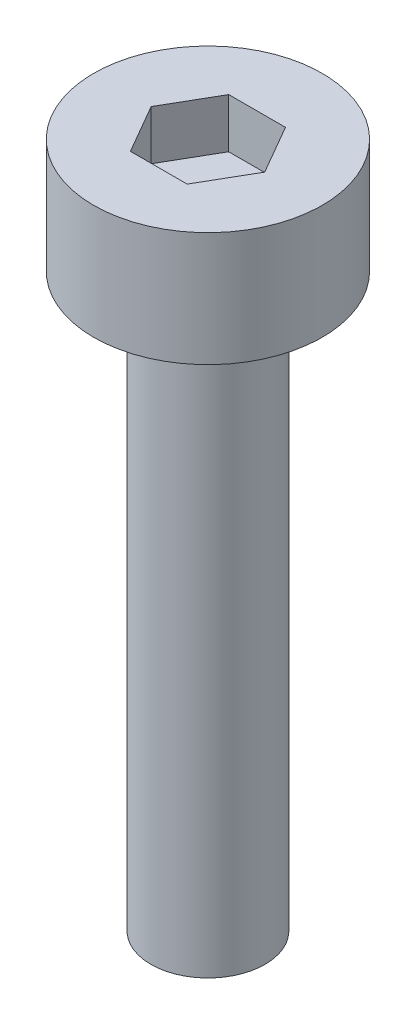
SolidWorks part; units mm, degrees
ref_plane "Front Plane" through (0, 0, 0) normal (0, 0, 1) x (1, 0, 0)
ref_plane "Top Plane" through (0, 0, 0) normal (0, 1, 0) x (1, 0, 0)
ref_plane "Right Plane" through (0, 0, 0) normal (1, 0, 0) x (0, 0, -1)
sketch "Sketch1" plane through (0, 0, 0) normal (0, 1, 0) x (1, 0, 0)
  circle A0 centre (0, 0) radius 1.5
  dimension "D1" = 3
extrude "ScrewShaft" add sketch "Sketch1" along normal blind 15
sketch "Sketch2" plane through (0, 15, 0) normal (0, 1, 0) x (1, 0, 0)
  circle A0 centre (0, 0) radius 3
  dimension "D1" = 6
extrude "Boss-Extrude2" add sketch "Sketch2" along normal blind 3
sketch "Sketch3" plane through (0, 18, 0) normal (0, 1, 0) x (1, 0, 0)
  line L0 (0, 0) -> (0, 1.29) construction
  line L1 (1.4896, 0) -> (0.7448, 1.29)
  line L2 (0.7448, 1.29) -> (-0.7448, 1.29)
  line L3 (-0.7448, 1.29) -> (-1.4896, 0)
  line L4 (-1.4896, 0) -> (-0.7448, -1.29)
  line L5 (-0.7448, -1.29) -> (0.7448, -1.29)
  line L6 (0.7448, -1.29) -> (1.4896, 0)
  circle A0 centre (0, 0) radius 1.29 construction
  dimension "D1" = 2.58
extrude "Cut-Extrude1" cut sketch "Sketch3" against normal blind 1.3
equation "\"X-ROD-SPACING\"=45"
equation "\"Y-ROD-SPACING\"=75"
equation "\"Z-ROD-SPACING\"=17.5"
equation "\"Y-BED-OFFSET\"=2"
equation "\"Y-BED-ROD-INSET\"=3.5"
equation "\"T-SLOT-NUT-FILLET-RADIUS\"=0.25"
equation "\"T-SLOT-SCREW-SHAFT-RADIUS\"=1.75"
equation "\"T-SLOT-SCREW-SHAFT-CUTOUT-LENGTH\"=10.5"
equation "\"T-SLOT-NUT-DEPTH\"=4.2"
equation "\"T-SLOT-NUT-WIDTH\"=3"
equation "\"T-SLOT-NUT-END-DISTANCE\"=8"
equation "\"ACRYLIC-THICKNESS\"=10"
equation "\"ACRYLIC-THICKNESS2\"=4.5"
equation "\"ACRYLIC-TAB-CUTOUT-SIZE\"=\"ACRYLIC-THICKNESS\"+\"ACRYLIC-TAB-TOLERANCE\"*2"
equation "\"ACRYLIC-TAB-WIDTH\"=\"ACRYLIC-THICKNESS\""
equation "\"ACRYLIC-M3-HOLE\"=3.1"
equation "\"SMOOTHROD-CAP-SCREW-DISTANCE\"=20"
equation "\"FRAME-WIDTH-INNER\"=370"
equation "\"NEMA17-HOLE-SPACING\"=31"
equation "\"NEMA17-CENTRAL-CUTOUT\"=22.5"
equation "\"Z-BRACKET-REACH\"=55"
equation "\"TOP-BRACKET-SPACING\"=40"
equation "\"SMOOTHROD-X-LENGTH\"=350"
equation "\"SMOOTHROD-Y-LENGTH\"=350"
equation "\"SMOOTHROD-Z-LENGTH\"=350"
equation "\"SMOOTHROD-TIGHTENING-HEADROOM\"=.25"
equation "\"LEADSCREW-Z-LENGTH\"=300"
equation "\"SCREW-LENGTH-FRAME\"=\"ACRYLIC-THICKNESS\" + 10"
equation "\"SCREW-HEAD-RADIUS\"=6"
equation "\"PRINTED-X-SMOOTHROD-DIAMETER\"=8.2"
equation "\"PRINTED-X-SMOOTHROD-CUTOUT\"=10"
equation "\"PRINTED-X-BASE-HEIGHT\"=10"
equation "\"PRINTED-LM8UU-CUTOUT-SIZE\"=15.25"
equation "\"PRINTED-LM8UU-CUTOUT-LENGTH\"=24.5"
equation "\"PRINTED-X-IDLER-HEIGHT\"=16"
equation "\"PSU-MOUNTING-WIDTH\"=95"
equation "\"PSU-MOUNTING-HEIGHT\"=177"
equation "\"D1@ScrewShaft\"=\"SCREW-LENGTH-MOTOR\""
equation "\"D1@Sketch2\"=\"SCREW-HEAD-RADIUS\""
equation "\"Y-BED-SCREW-SPACING\"=209"
equation "\"Y-BED-SCREW-CUTOUT-SLOT-HEIGHT\"=2"
equation "\"Z-ROD-INSET\"=16"
equation "\"SCREW-LENGTH-MOTOR\"=\"ACRYLIC-THICKNESS\" + 5"
equation "\"Y-BELT-TO-ROD-DISTANCE\"=20"
equation "\"SPOOL-HOLDER-ROD-SPACING\"=150"
